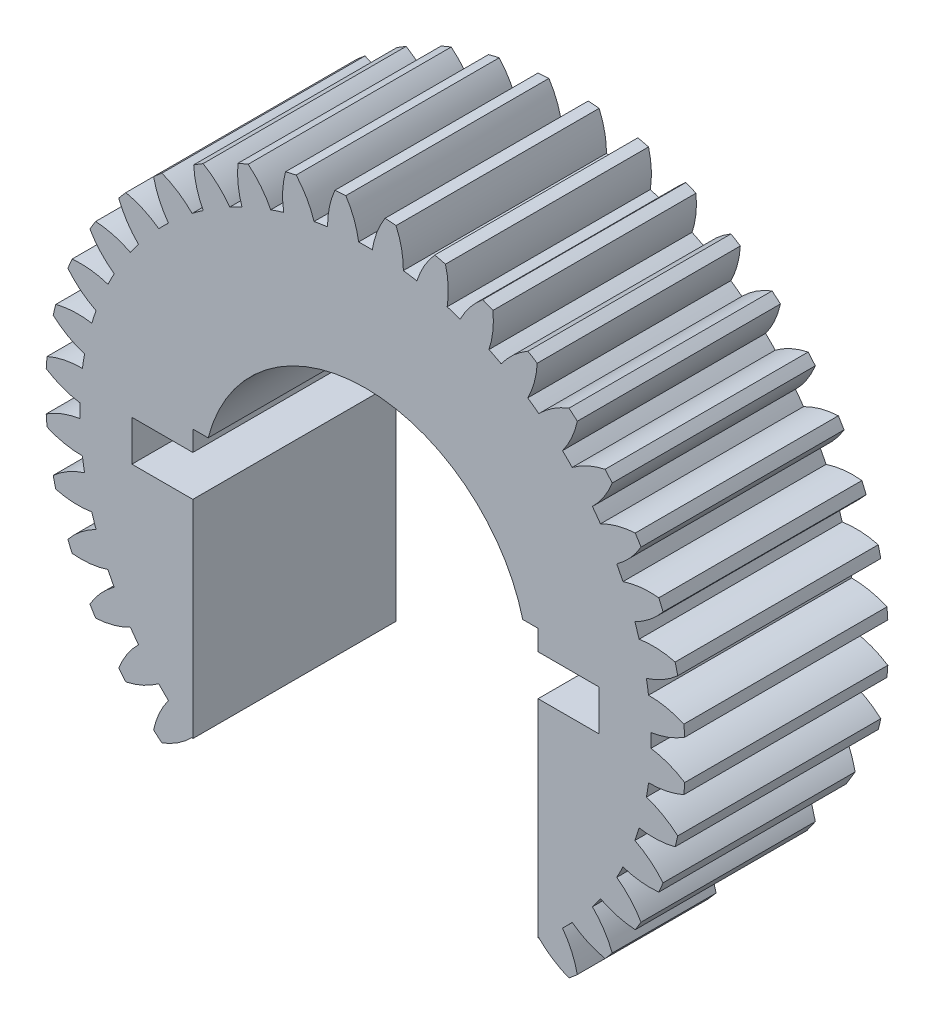
SolidWorks part; units mm, degrees
ref_plane "Front" through (0, 0, 0) normal (0, 0, 1) x (1, 0, 0)
ref_plane "Top" through (0, 0, 0) normal (0, 1, 0) x (1, 0, 0)
ref_plane "Right" through (0, 0, 0) normal (1, 0, 0) x (0, 0, -1)
sketch "Эскиз9" plane through (0, 0, 0) normal (0, 0, 1) x (1, 0, 0)
  circle A0 centre (0, 0) radius 14.0625 construction
  circle A1 centre (0, 0) radius 14.095 construction
  circle A2 centre (0, 0) radius 15 construction
  circle A3 centre (0, 0) radius 15.75
  dimension "D1" = 28.125
  dimension "D2" = 28.19
  dimension "D3" = 30
  dimension "D4" = 31.5
extrude "Бобышка-Вытянуть2" add sketch "Эскиз9" along normal mid plane 10
sketch "Эскиз10" plane through (0, 0, 0) normal (0, 0, 1) x (1, 0, 0)
  line L0 (-0.7335, 16.6765) -> (0, 0) construction
  line L1 (-0.6674, 15.1728) -> (-5.819, 12.8378) construction
  line L2 (-0.589, 14.9884) -> (0.589, 14.9884) construction
  line L3 (0, 0) -> (0, 15.75) construction
  circle A0 centre (0, 0) radius 15.75 construction
  circle A1 centre (0, 0) radius 14.095 construction
  arc A2 (-1.3223, 16.1961) -> (-0.3371, 14.0585) centre (-4.5302, 13.422) cw
  circle A3 centre (0, 0) radius 14.0625 construction
  circle A4 centre (0, 0) radius 15 construction
  arc A5 (1.3223, 16.1961) -> (0.3371, 14.0585) centre (4.5302, 13.422) ccw
  arc A7 (0.3371, 14.0585) -> (-0.3371, 14.0585) centre (0, 0) ccw
  circle A8 centre (0, 0) radius 16.25
  arc A9 (1.3223, 16.1961) -> (-1.3223, 16.1961) centre (0, 0) ccw
  point P3 (-0.6674, 15.1728)
  dimension "D1" = 0.5625
  dimension "D2" = 1.178
  dimension "D3" = 5.6561
  dimension "D4" = 1.415
  dimension "D5" = 0.5
sketch "Эскиз11" plane through (0, 0, 0) normal (0, 1, 0) x (1, 0, 0)
  line L0 (0, 5) -> (0, -5)
  line L1 (15.75, 5) -> (-15.75, 5) construction
  line L2 (-15.75, -5) -> (15.75, -5) construction
  line L3 (0, -50) -> (0, 50) construction
  dimension "D1" = 0
curve "Кривая2"
sketch "Эскиз12" plane through (0, 0, 5) normal (0, 0, 1) x (1, 0, 0)
  line L0 (-0.7335, 16.6765) -> (0, 0) construction
  line L1 (-0.6674, 15.1728) -> (-5.819, 12.8378) construction
  line L2 (-0.589, 14.9884) -> (0.589, 14.9884) construction
  line L3 (0, 0) -> (0, 15.75) construction
  arc A2 (-1.3223, 16.1961) -> (-0.3371, 14.0585) centre (-4.5302, 13.422) cw
  arc A5 (1.3223, 16.1961) -> (0.3371, 14.0585) centre (4.5302, 13.422) ccw
  arc A7 (0.3371, 14.0585) -> (-0.3371, 14.0585) centre (0, 0) ccw
  arc A9 (1.3223, 16.1961) -> (-1.3223, 16.1961) centre (0, 0) ccw
  point P3 (-0.6674, 15.1728)
sketch "Эскиз13" plane through (0, 0, -5) normal (0, 0, 1) x (1, 0, 0)
  line L0 (-0.7335, 16.6765) -> (0, 0) construction
  line L1 (-0.6674, 15.1728) -> (-5.819, 12.8378) construction
  line L2 (-0.589, 14.9884) -> (0.589, 14.9884) construction
  line L3 (0, 0) -> (0, 15.75) construction
  arc A2 (-1.3223, 16.1961) -> (-0.3371, 14.0585) centre (-4.5302, 13.422) cw
  arc A5 (1.3223, 16.1961) -> (0.3371, 14.0585) centre (4.5302, 13.422) ccw
  arc A7 (0.3371, 14.0585) -> (-0.3371, 14.0585) centre (0, 0) ccw
  arc A9 (1.3223, 16.1961) -> (-1.3223, 16.1961) centre (0, 0) ccw
  point P3 (-0.6674, 15.1728)
loft "Вырез-По сечениям2" cut profiles "Эскиз12", "Эскиз10", "Эскиз13" start constraint default end constraint default
pattern_circular "Круговой массив1" count 40 over 360 about axis through (0, 0, 5) along (0, 0, -1) of "Вырез-По сечениям2"
sketch "Эскиз14" plane through (0, 0, -5) normal (0, 0, -1) x (-1, 0, 0)
  line L0 (0, 0) -> (0, -16.7062) construction
  line L1 (-11.5, 1) -> (11.5, 1)
  line L2 (-11.5, 1) -> (-11.5, -1)
  line L3 (-11.5, -1) -> (11.5, -1)
  line L4 (11.5, 1) -> (11.5, -1)
  line L5 (-11.5, 1) -> (11.5, -1) construction
  line L6 (-11.5, -1) -> (11.5, 1) construction
  line L7 (-8.5, 2) -> (8.5, 2)
  line L8 (-8.5, 2) -> (-8.5, -18)
  line L9 (-8.5, -18) -> (8.5, -18)
  line L10 (8.5, 2) -> (8.5, -18)
  circle A0 centre (0, 0) radius 8
  dimension "D1" = 16
  dimension "D2" = 2
  dimension "D3" = 23
  dimension "D4" = 17
  dimension "D5" = 20
  dimension "D6" = 1
extrude "Вырез-Вытянуть1" cut sketch "Эскиз14" against normal through all contours L3 A0 | L8 L1 L2 L3 | L1 L10 L3 L4 | L7 A0 | L1 A0 L7 | L1 A0 L3 | L7 L10 L9 L8 region at (10, 0, -5) region at (0, 1.498, -5) region at (0, 0, -5) region at (0, 4.4991, -5) region at (0, -3.9418, -5) region at (-10, 0, -5)
sketch "Эскиз15" plane through (25.5, 0, 0) normal (1, 0, 0) x (0, 0, -1)
  circle A0 centre (17, -12) radius 14
extrude "Вырез-Вытянуть2" cut sketch "Эскиз15" against normal blind 20
sketch "Эскиз16" plane through (12.5, 0, 0) normal (1, 0, 0) x (0, 0, -1)
  circle A0 centre (17, -12) radius 17
extrude "Вырез-Вытянуть3" cut sketch "Эскиз16" against normal blind 10
